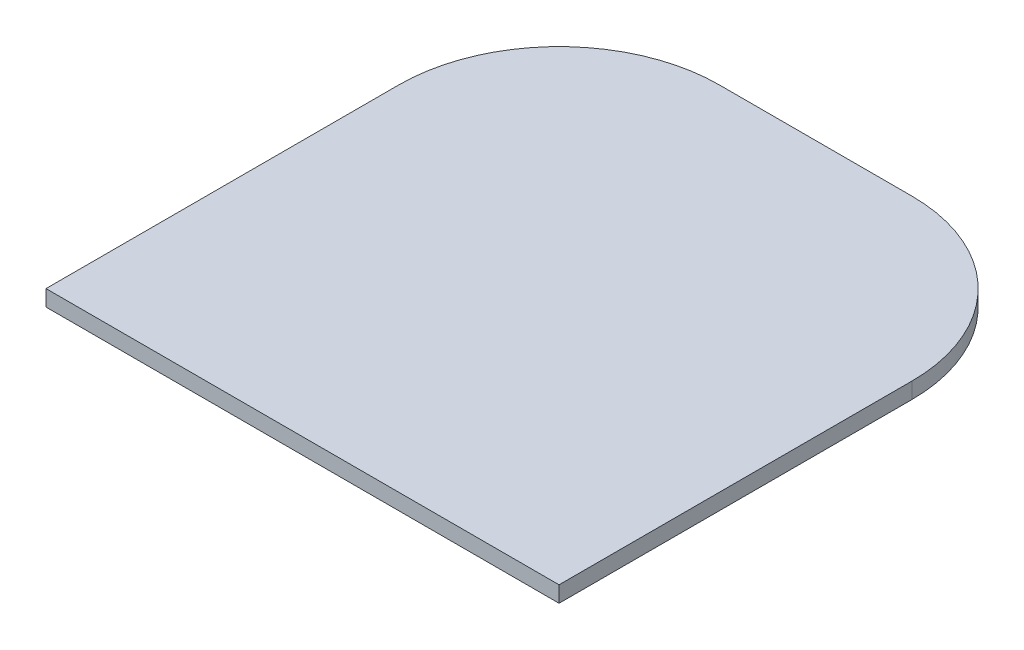
SolidWorks part; units mm, degrees
material "Acrylic (Medium-high impact)"
ref_plane "Front Plane" through (0, 0, 0) normal (0, 0, 1) x (1, 0, 0)
ref_plane "Top Plane" through (0, 0, 0) normal (0, 1, 0) x (1, 0, 0)
ref_plane "Right Plane" through (0, 0, 0) normal (1, 0, 0) x (0, 0, -1)
sketch "Sketch1" plane through (0, 0, 0) normal (0, 1, 0) x (1, 0, 0)
  line L1 (-101.6, -101.6) -> (101.6, -101.6)
  line L2 (-101.6, -101.6) -> (-101.6, 101.6)
  line L3 (-101.6, 101.6) -> (101.6, 101.6)
  line L4 (101.6, -101.6) -> (101.6, 101.6)
  line L5 (-101.6, -101.6) -> (101.6, 101.6) construction
  line L6 (-101.6, 101.6) -> (101.6, -101.6) construction
  point P0 (0, 0)
  dimension "D1" = 203.2
  dimension "D2" = 203.2
extrude "Boss-Extrude1" add sketch "Sketch1" along normal blind 6.35
sketch "Sketch2" plane through (0, 6.35, 0) normal (0, 1, 0) x (1, 0, 0)
  line L9 (101.6, 38.1) -> (101.6, 101.6)
  line L10 (101.6, 101.6) -> (38.1, 101.6)
  line L11 (-38.1, 101.6) -> (-101.6, 101.6)
  line L12 (-101.6, 101.6) -> (-101.6, 38.1)
  arc A2 (101.6, 38.1) -> (38.1, 101.6) centre (38.1, 38.1) ccw
  arc A3 (-101.6, 38.1) -> (-38.1, 101.6) centre (-38.1, 38.1) cw
extrude "Cut-Extrude1" cut sketch "Sketch2" against normal through all
